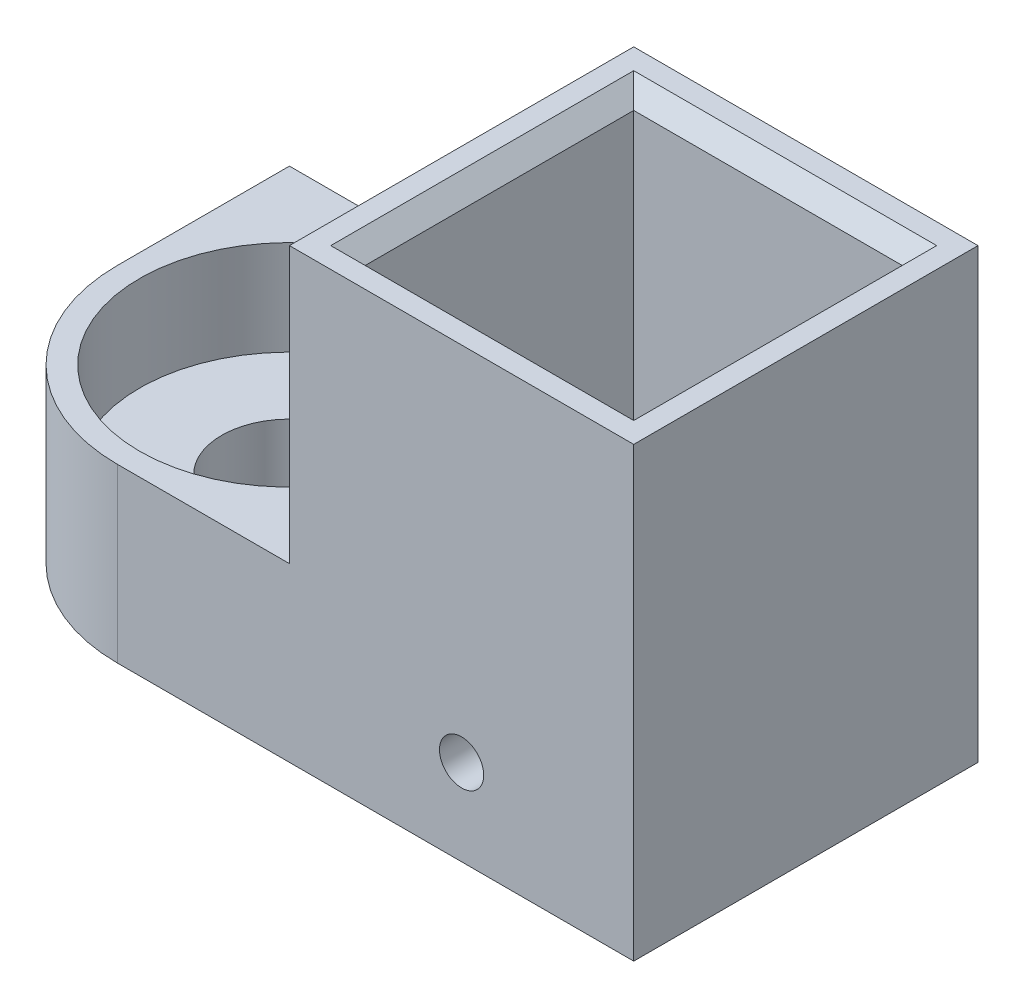
SolidWorks part; units mm, degrees
ref_plane "Front Plane" through (0, 0, 0) normal (0, 0, 1) x (1, 0, 0)
ref_plane "Top Plane" through (0, 0, 0) normal (0, 1, 0) x (1, 0, 0)
ref_plane "Right Plane" through (0, 0, 0) normal (1, 0, 0) x (0, 0, -1)
sketch "Sketch1" plane through (0, 0, 0) normal (0, 1, 0) x (1, 0, 0)
  line L1 (-12.7, 12.7) -> (12.7, 12.7)
  line L2 (-12.7, 12.7) -> (-12.7, -12.7)
  line L3 (-12.7, -12.7) -> (12.7, -12.7)
  line L4 (12.7, 12.7) -> (12.7, -12.7)
  line L5 (-12.7, 12.7) -> (12.7, -12.7) construction
  line L6 (-12.7, -12.7) -> (12.7, 12.7) construction
  line L7 (-9.906, -9.906) -> (9.906, -9.906)
  line L8 (-9.906, -9.906) -> (-9.906, 9.906)
  line L9 (-9.906, 9.906) -> (9.906, 9.906)
  line L10 (9.906, -9.906) -> (9.906, 9.906)
  line L11 (-9.906, -9.906) -> (9.906, 9.906) construction
  line L12 (-9.906, 9.906) -> (9.906, -9.906) construction
  point P0 (0, 0)
  point P6 (0, 0)
  dimension "D1" = 25.4
  dimension "D2" = 19.812
extrude "Boss-Extrude1" add sketch "Sketch1" along normal blind 33.02
sketch "Sketch9" plane through (0, 0, 0) normal (0, -1, 0) x (1, 0, 0)
  line L0 (-12.7, -12.7) -> (-12.7, 12.7) construction
  line L1 (-12.7, -12.7) -> (-12.7, 12.7)
  line L2 (-12.7, 12.7) -> (-38.1, 12.7)
  line L3 (-38.1, 12.7) -> (-38.1, -12.7)
  line L4 (-38.1, -12.7) -> (-12.7, -12.7)
  dimension "D1" = 25.4
extrude "Boss-Extrude5" add sketch "Sketch9" against normal blind 12.7
sketch "Sketch10" plane through (0, 12.7, 0) normal (0, 1, 0) x (1, 0, 0)
  line L0 (-38.1, 12.7) -> (-12.7, 12.7) construction
  line L1 (-38.1, -12.7) -> (-38.1, 12.7) construction
  circle A0 centre (-25.4, 0) radius 11.049
  point P4 (-25.4, 12.7)
  point P7 (-38.1, 0)
  dimension "D1" = 22.098
sketch "Sketch14" plane through (0, 0, 0) normal (0, -1, 0) x (1, 0, 0)
  line L0 (9.906, 9.906) -> (9.906, -9.906) construction
  line L1 (-9.906, 9.906) -> (9.906, 9.906) construction
  line L2 (-9.906, -9.906) -> (-9.906, 9.906) construction
  line L3 (9.906, -9.906) -> (-9.906, -9.906) construction
  line L4 (9.906, 9.906) -> (9.906, -9.906)
  line L5 (-9.906, 9.906) -> (9.906, 9.906)
  line L6 (-9.906, -9.906) -> (-9.906, 9.906)
  line L7 (9.906, -9.906) -> (-9.906, -9.906)
  line L8 (-8.001, 8.001) -> (8.001, 8.001)
  line L9 (8.001, 8.001) -> (8.001, -8.001)
  line L10 (8.001, -8.001) -> (-8.001, -8.001)
  line L11 (-8.001, -8.001) -> (-8.001, 8.001)
  dimension "D1" = 1.905
extrude "Boss-Extrude6" add sketch "Sketch14" against normal blind 2.54
extrude "Cut-Extrude1" cut sketch "Sketch10" against normal blind 7
sketch "Sketch15" plane through (0, 5.7, 0) normal (0, 1, 0) x (1, 0, 0)
  circle A0 centre (-25.4, 0) radius 5
  circle A1 centre (-25.4, 0) radius 11.049 construction
  dimension "D1" = 10
extrude "Cut-Extrude2" cut sketch "Sketch15" against normal up to next
sketch "Sketch17" plane through (0, 0, 0) normal (0, -1, 0) x (1, 0, 0)
  line L0 (-12.7, -12.7) -> (-12.7, 12.7) construction
  line L1 (-38.1, -12.7) -> (-12.7, -12.7)
  line L2 (-38.1, -12.7) -> (-38.1, -38.1)
  line L3 (-38.1, -38.1) -> (-12.7, -38.1)
  line L4 (-12.7, -12.7) -> (-12.7, -38.1)
  dimension "D1" = 25.4
extrude "Boss-Extrude7" add sketch "Sketch17" against normal blind 6.35
sketch "Sketch18" plane through (0, 0, 0) normal (0, -1, 0) x (1, 0, 0)
  line L0 (-38.1, -38.1) -> (-12.7, -38.1) construction
  line L1 (-12.7, -38.1) -> (-12.7, -12.7) construction
  circle A0 centre (-25.4, -25.4) radius 6.5
  point P4 (-25.4, -38.1)
  point P7 (-12.7, -25.4)
  dimension "D1" = 13
extrude "Cut-Extrude4" cut sketch "Sketch18" against normal up to next
hole_wizard "M3 Clearance Hole1" positions "Sketch20" profile "Sketch22" hole size "M3" standard "ANSI Metric"
sketch "Sketch20" plane through (0, 0, 0) normal (0, -1, 0) x (-1, 0, 0)
  line L0 (12.7, 38.1) -> (12.7, 12.7) construction
  circle A0 centre (25.4, 25.4) radius 6.5 construction
  point P0 (16.4, 25.4)
  point P5 (12.7, 25.4)
  dimension "D1" = 9
sketch "Sketch22" plane through (-16.4, 0, -25.4) normal (1, 0, 0) x (0, 0, -1)
  line L0 (0, 0) -> (0, 13.7215)
  line L1 (0, 13.7215) -> (1.7, 12.7)
  line L2 (1.7, 12.7) -> (1.7, 0)
  line L5 (1.7, 0) -> (0, 0)
  line L10 (0, 13.7215) -> (-1.7, 12.7) construction
  line L11 (0, -6.35) -> (0, 107.95) construction
  dimension "Hole Dia." = 3.4
  dimension "Hole Depth" = 12.7
  dimension "Drill Angle" = 118
pattern_circular "CirPattern1" count 4 over 360 about axis through (-25.4, 0, -25.4) along (0, -1, 0) of "M3 Clearance Hole1"
sketch "Sketch23" plane through (0, 6.35, 0) normal (0, 1, 0) x (1, 0, 0)
  circle A0 centre (-25.4, 34.4) radius 3.25
  circle A1 centre (-25.4, 34.4) radius 1.7 construction
  dimension "D1" = 6.5
extrude "Cut-Extrude5" cut sketch "Sketch23" against normal blind 2.75
pattern_circular "CirPattern2" count 4 over 360 about axis through (-25.4, 33.021, -25.4) along (0, -1, 0) of "Cut-Extrude5" reverse direction yes
fillet "Fillet3" radius 12.7 3 edges at (-38.1, 3.175, -38.1) (-12.7, 3.175, -38.1) (-38.1, 6.35, 12.7)
fillet "Fillet4" radius 1.27 4 edges at (8.001, 1.27, -8.001) (8.001, 1.27, 8.001) (-8.001, 1.27, 8.001) (-8.001, 1.27, -8.001)
fillet "Fillet5" radius 1.27 16 edges at (-7.629, 2.54, -7.629) (-8.001, 2.54, 0) (-7.629, 2.54, 7.629) (0, 2.54, 8.001) (7.629, 2.54, 7.629) (8.001, 2.54, 0) (7.629, 2.54, -7.629) (-7.629, 0, -7.629) (-8.001, 0, 0) (-7.629, 0, 7.629) (0, 0, 8.001) (7.629, 0, 7.629) (8.001, 0, 0) (7.629, 0, -7.629) (0, 2.54, -8.001) (0, 0, -8.001)
hole_wizard "#4 Clearance Hole1" positions "Sketch24" profile "Sketch25" hole size "#4" standard "ANSI Inch" end condition through all
sketch "Sketch24" plane through (0, 0, 12.7) normal (0, 0, 1) x (1, 0, 0)
  line L0 (-25.4, 0) -> (12.7, 0) construction
  line L1 (-9.906, 33.02) -> (9.906, 33.02) construction
  point P0 (0, 6.35)
  point P10 (0, 33.02)
  dimension "D1" = 6.35
sketch "Sketch25" plane through (0, 6.35, 12.7) normal (1, 0, 0) x (0, -1, 0)
  line L0 (0, 0) -> (0, 50.8)
  line L1 (0, 50.8) -> (1.6319, 50.8)
  line L2 (1.6319, 50.8) -> (1.6319, 0)
  line L5 (1.6319, 0) -> (0, 0)
  line L11 (0, -6.35) -> (0, 107.95) construction
  dimension "Thru Hole Dia." = 3.2639
  dimension "Thru Hole Depth" = 50.8
chamfer "Chamfer1" distance 1.27 angle 45 4 edges at (-9.906, 33.02, 0) (0, 33.02, 9.906) (0, 33.02, -9.906) (9.906, 33.02, 0)
equation "\"TOL\"= .01"
equation "\"D2@Sketch1\"=.76+\"TOL\"*2"
